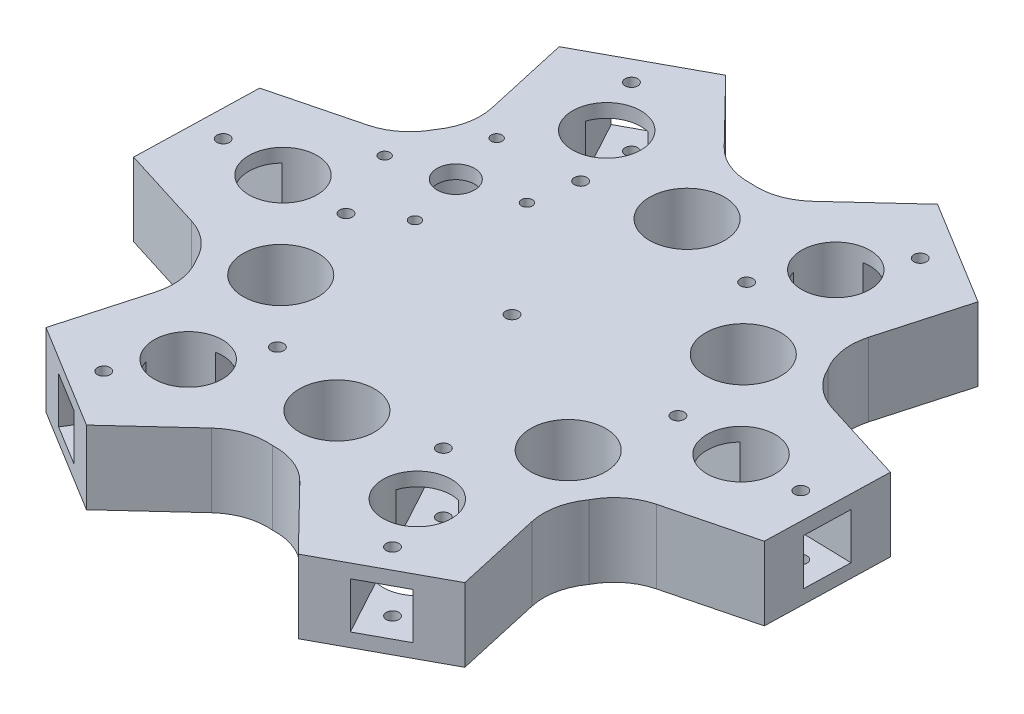
SolidWorks part; units mm, degrees
ref_plane "Alzado" through (0, 0, 0) normal (0, 0, 1) x (1, 0, 0)
ref_plane "Planta" through (0, 0, 0) normal (0, 1, 0) x (1, 0, 0)
ref_plane "Vista lateral" through (0, 0, 0) normal (1, 0, 0) x (0, 0, -1)
sketch "Croquis2" plane through (0, 0, 0) normal (0, 1, 0) x (1, 0, 0)
  line L0 (-14.424, -110.7546) -> (9.8666, -107.5585) construction
  line L1 (0, 0) -> (55.8116, 90.9663) construction
  line L2 (34.3385, 90.3873) -> (65.0234, 71.5609)
  line L3 (0, 0) -> (93.8174, 50.8733) construction
  line L4 (0, 0) -> (106.6849, -2.8511) construction
  line L5 (0, 0) -> (90.9663, -55.8116) construction
  line L6 (0, 0) -> (50.8733, -93.8174) construction
  line L7 (0, 0) -> (-2.8511, -106.6849) construction
  line L8 (0, 0) -> (-55.8116, -90.9663) construction
  line L9 (0, 0) -> (-93.8174, -50.8733) construction
  line L10 (0, 0) -> (-106.6849, 2.8511) construction
  line L11 (0, 0) -> (-90.9663, 55.8116) construction
  line L12 (0, 0) -> (-50.8733, 93.8174) construction
  line L13 (0, 0) -> (2.8511, 106.6849) construction
  line L14 (65.0234, 71.5609) -> (57.9987, 46.5578)
  line L15 (34.3385, 90.3873) -> (15.2308, 72.7977)
  line L16 (95.447, 15.4557) -> (70.6601, 23.2086)
  line L17 (95.447, 15.4557) -> (94.4852, -20.5315)
  line L18 (94.4852, -20.5315) -> (69.3196, -26.9494)
  line L19 (61.1085, -74.9317) -> (55.4292, -49.5891)
  line L20 (61.1085, -74.9317) -> (29.4618, -92.0923)
  line L21 (29.4618, -92.0923) -> (11.3209, -73.5073)
  line L22 (-34.3385, -90.3873) -> (-15.2308, -72.7977)
  line L23 (-34.3385, -90.3873) -> (-65.0234, -71.5609)
  line L24 (-65.0234, -71.5609) -> (-57.9987, -46.5578)
  line L25 (-95.447, -15.4557) -> (-70.6601, -23.2086)
  line L26 (-95.447, -15.4557) -> (-94.4852, 20.5315)
  line L27 (-94.4852, 20.5315) -> (-69.3196, 26.9494)
  line L28 (-61.1085, 74.9317) -> (-55.4292, 49.5891)
  line L29 (-61.1085, 74.9317) -> (-29.4618, 92.0923)
  line L30 (-29.4618, 92.0923) -> (-11.3209, 73.5073)
  circle A0 centre (45.4973, 74.1552) radius 1.85
  circle A1 centre (26.1479, 42.6179) radius 1.85
  circle A2 centre (36.084, 58.8128) radius 10
  circle A3 centre (0, 0) radius 1.85
  arc A4 (57.9987, 46.5578) -> (60.0714, 32.5743) centre (74.6477, 41.8802) ccw
  arc A5 (15.2308, 72.7977) -> (1.8256, 68.3105) centre (3.5182, 85.5211) cw
  circle A6 centre (43.9537, 23.8343) radius 11
  arc A7 (70.6601, 23.2086) -> (60.0714, 32.5743) centre (75.8226, 39.7137) cw
  arc A8 (69.3196, -26.9494) -> (58.2459, -35.7362) centre (73.5932, -43.7067) ccw
  circle A9 centre (68.9754, -1.8433) radius 10
  circle A10 centre (86.9689, -2.3242) radius 1.85
  circle A11 centre (49.9822, -1.3357) radius 1.85
  circle A12 centre (42.6179, -26.1479) radius 11
  arc A13 (55.4292, -49.5891) -> (58.2459, -35.7362) centre (72.3043, -45.8074) cw
  arc A14 (11.3209, -73.5073) -> (-1.8256, -68.3105) centre (-1.0545, -85.5869) ccw
  circle A15 centre (32.8913, -60.6561) radius 10
  circle A16 centre (41.4717, -76.4794) radius 1.85
  circle A17 centre (23.8343, -43.9537) radius 1.85
  circle A18 centre (-1.3357, -49.9822) radius 11
  arc A19 (-15.2308, -72.7977) -> (-1.8256, -68.3105) centre (-3.5182, -85.5211) cw
  arc A20 (-57.9987, -46.5578) -> (-60.0714, -32.5743) centre (-74.6477, -41.8802) ccw
  circle A21 centre (-36.084, -58.8128) radius 10
  circle A22 centre (-45.4973, -74.1552) radius 1.85
  circle A23 centre (-26.1479, -42.6179) radius 1.85
  circle A24 centre (-43.9537, -23.8343) radius 11
  arc A25 (-70.6601, -23.2086) -> (-60.0714, -32.5743) centre (-75.8226, -39.7137) cw
  arc A26 (-69.3196, 26.9494) -> (-58.2459, 35.7362) centre (-73.5932, 43.7067) ccw
  circle A27 centre (-68.9754, 1.8433) radius 10
  circle A28 centre (-86.9689, 2.3242) radius 1.85
  circle A29 centre (-49.9822, 1.3357) radius 1.85
  circle A30 centre (-42.6179, 26.1479) radius 11
  arc A31 (-55.4292, 49.5891) -> (-58.2459, 35.7362) centre (-72.3043, 45.8074) cw
  arc A32 (-11.3209, 73.5073) -> (1.8256, 68.3105) centre (1.0545, 85.5869) ccw
  circle A33 centre (-32.8913, 60.6561) radius 10
  circle A34 centre (-41.4717, 76.4794) radius 1.85
  circle A35 centre (-23.8343, 43.9537) radius 1.85
  circle A36 centre (1.3357, 49.9822) radius 11
  point P9 (49.6809, 80.9741)
  point P28 (0, 0)
  point P117 (0, 0)
  dimension "D4" = 3.7
  dimension "D5" = 3.7
  dimension "D8" = 20
  dimension "D10" = 3.7
  dimension "D12" = 22
  dimension "D1" = 24.5
  dimension "D2" = 36
  dimension "D3" = 95
  dimension "D6" = 87
  dimension "D7" = 50
  dimension "D9" = 18
  dimension "D13" = 50
  dimension "D11" = 12
  dimension "D14" = 6
extrude "Saliente-Extruir1" add sketch "Croquis2" along normal blind 21.5
sketch "Croquis3" plane through (45.2852, 0, 83.512) normal (0.4767, 0, 0.8791) x (0.8791, 0, -0.4767)
  line L0 (-18, 21.5) -> (18, 21.5) construction
  line L1 (-6.75, 17.5) -> (6.75, 17.5)
  line L2 (-6.75, 17.5) -> (-6.75, 4)
  line L3 (-6.75, 4) -> (6.75, 4)
  line L4 (6.75, 17.5) -> (6.75, 4)
  line L5 (-6.75, 17.5) -> (6.75, 4) construction
  line L6 (-6.75, 4) -> (6.75, 17.5) construction
  line L7 (18, 21.5) -> (18, 0) construction
  point P0 (0, 10.75)
  dimension "D1" = 13.5
  dimension "D2" = 13.5
  dimension "D3" = 4
  dimension "D4" = 11.25
extrude "Cortar-Extruir1" cut sketch "Croquis3" against normal through all
pattern_circular "MatrizC1" count 6 over 360 about axis through (0, 4, 0) along (0, -1, 0) of "Cortar-Extruir1"
sketch "Croquis4" plane through (0, 21.5, 0) normal (0, 1, 0) x (1, 0, 0)
  circle A0 centre (-42.6179, 26.1479) radius 5.5
  circle A1 centre (-42.6179, 26.1479) radius 11
  dimension "D1" = 11
extrude "Saliente-Extruir2" add sketch "Croquis4" against normal blind 4
sketch "Croquis5" plane through (0, 21.5, 0) normal (0, 1, 0) x (1, 0, 0)
  circle A0 centre (-47.0566, 42.5582) radius 1.6
  circle A1 centre (-42.6179, 26.1479) radius 5.5 construction
  circle A2 centre (-42.6179, 26.1479) radius 5.5
  circle A3 centre (-26.2076, 30.5865) radius 1.6
  circle A4 centre (-38.1793, 9.7376) radius 1.6
  circle A5 centre (-59.0283, 21.7092) radius 1.6
  point P14 (-42.6179, 26.1479)
  dimension "D1" = 3.2
  dimension "D2" = 17
  dimension "D3" = 4
extrude "Cortar-Extruir2" cut sketch "Croquis5" against normal blind 10
